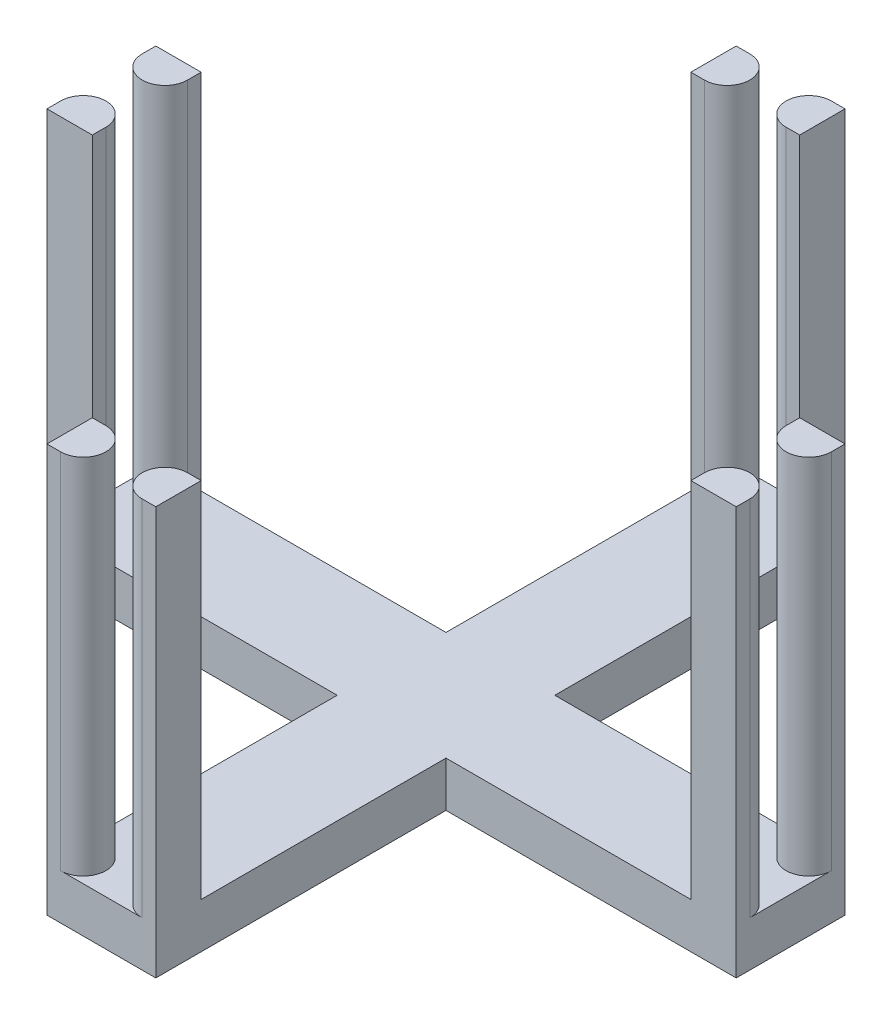
SolidWorks part; units mm, degrees
ref_plane "Front Plane" through (0, 0, 0) normal (0, 0, 1) x (1, 0, 0)
ref_plane "Top Plane" through (0, 0, 0) normal (0, 1, 0) x (1, 0, 0)
ref_plane "Right Plane" through (0, 0, 0) normal (1, 0, 0) x (0, 0, -1)
sketch "Sketch1" plane through (0, 0, 0) normal (0, 1, 0) x (1, 0, 0)
  line L0 (-3, 3) -> (-3, 19)
  line L1 (3, -19) -> (-3, -19)
  line L2 (3, -19) -> (3, -3)
  line L3 (3, 19) -> (-3, 19)
  line L4 (-3, -19) -> (-3, -3)
  line L5 (3, -19) -> (-3, 19) construction
  line L6 (3, 19) -> (-3, -19) construction
  line L7 (19, -3) -> (3, -3)
  line L8 (19, -3) -> (19, 3)
  line L9 (19, 3) -> (3, 3)
  line L10 (-19, -3) -> (-19, 3)
  line L11 (19, -3) -> (-19, 3) construction
  line L12 (19, 3) -> (-19, -3) construction
  line L13 (-3, 3) -> (-19, 3)
  line L15 (3, 3) -> (3, 19)
  line L18 (-3, -3) -> (-19, -3)
  point P0 (0, 0)
  point P6 (0, 0)
  dimension "D1" = 6
  dimension "D2" = 16
extrude "Boss-Extrude1" add sketch "Sketch1" along normal blind 2.5
sketch "Sketch2" plane through (0, 2.5, 0) normal (0, 1, 0) x (1, 0, 0)
  line L0 (-2.25, -19) -> (-3, -19)
  line L1 (-3, -19) -> (3, -19) construction
  line L2 (-3, -19) -> (-3, -16.5)
  line L3 (-3, -3) -> (-3, -19) construction
  line L4 (0, -19) -> (0, 19) construction
  line L5 (3, 19) -> (-3, 19) construction
  line L6 (-3, -16.5) -> (-2.25, -16.5)
  line L7 (3, -16.5) -> (2.25, -16.5)
  line L8 (3, -19) -> (3, -16.5)
  line L9 (2.25, -19) -> (3, -19)
  arc A0 (-2.25, -19) -> (-2.25, -16.5) centre (-2.25, -17.75) ccw
  arc A1 (2.25, -19) -> (2.25, -16.5) centre (2.25, -17.75) cw
  dimension "D1" = 4.5
  dimension "D2" = 0.75
  dimension "D3" = 2.5
extrude "Boss-Extrude2" add sketch "Sketch2" along normal blind 20
ref_axis "Axis1" through (0, 0, 0) along (0, 1, 0)
pattern_circular "CirPattern1" count 4 over 360 about axis through (0, 0, 0) along (0, 1, 0) of "Boss-Extrude2"
sketch "Sketch3" plane through (0, 2.5, 0) normal (0, 1, 0) x (1, 0, 0)
  line L0 (0, 19) -> (0, 14.0065) construction
  line L1 (2.25, 19) -> (-2.25, 19) construction
  line L2 (-3, 17.75) -> (3, 17.75) construction
  line L3 (-3, 19) -> (-3, 16.5) construction
  line L4 (3, 16.5) -> (3, 19) construction
  line L5 (4.5, 21.5) -> (-4.5, 21.5)
  line L6 (3.5, 16) -> (0.75, 16)
  line L7 (3.5, 16) -> (3.5, 19.5)
  line L8 (3.5, 19.5) -> (0.75, 19.5)
  line L9 (-3.5, 16) -> (-3.5, 19.5)
  line L10 (3.5, 16) -> (-3.5, 19.5) construction
  line L11 (3.5, 19.5) -> (-3.5, 16) construction
  line L12 (-5.5, 15) -> (-5.5, 20.5)
  line L13 (4.5, 14) -> (-4.5, 14)
  line L14 (5.5, 15) -> (5.5, 20.5)
  line L15 (-0.75, 19.5) -> (-3.5, 19.5)
  line L16 (-5.5, 14) -> (-5.5, 21.5) construction
  line L17 (0.75, 16) -> (0.75, 19.5)
  line L18 (-0.75, 16) -> (-3.5, 16)
  line L19 (-0.75, 16) -> (-0.75, 19.5)
  line L20 (0.75, 16) -> (-0.75, 19.5) construction
  line L21 (0.75, 19.5) -> (-0.75, 16) construction
  line L22 (3.5, 19.5) -> (-3.5, 19.5) construction
  line L23 (3.5, 16) -> (-3.5, 16) construction
  line L24 (5.5, 14) -> (-5.5, 14) construction
  line L25 (5.5, 14) -> (5.5, 21.5) construction
  line L26 (5.5, 21.5) -> (-5.5, 21.5) construction
  arc A0 (-5.5, 15) -> (-4.5, 14) centre (-4.5, 15) ccw
  arc A1 (4.5, 14) -> (5.5, 15) centre (4.5, 15) ccw
  arc A2 (5.5, 20.5) -> (4.5, 21.5) centre (4.5, 20.5) ccw
  arc A3 (-5.5, 20.5) -> (-4.5, 21.5) centre (-4.5, 20.5) cw
  point P11 (0, 17.75)
  point P20 (0, 17.75)
  dimension "D5" = 1
  dimension "D1" = 3.5
  dimension "D2" = 7
  dimension "D4" = 1.5
  dimension "D3" = 2
